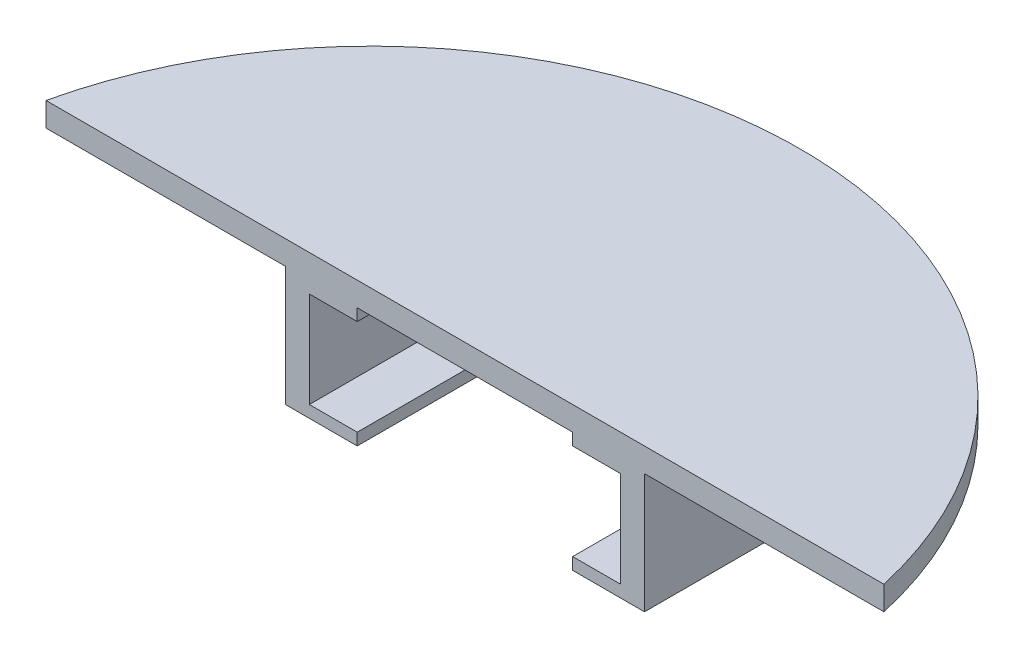
SolidWorks part; units mm, degrees
ref_plane "Front Plane" through (0, 0, 0) normal (0, 0, 1) x (1, 0, 0)
ref_plane "Top Plane" through (0, 0, 0) normal (0, 1, 0) x (1, 0, 0)
ref_plane "Right Plane" through (0, 0, 0) normal (1, 0, 0) x (0, 0, -1)
sketch "Sketch1" plane through (0, 0, 0) normal (0, 1, 0) x (1, 0, 0)
  line L0 (-13, 0) -> (-13, -13)
  line L1 (13, 0) -> (13, -13)
  line L2 (15, 0) -> (15, -13)
  line L3 (-15, 0) -> (-15, -13)
  line L4 (-35, -13) -> (35, -13)
  line L5 (-9, 0) -> (-9, -13)
  line L6 (9, 0) -> (9, -13)
  circle A0 centre (0, 0) radius 13 construction
  circle A2 centre (0, 0) radius 15 construction
  arc A3 (13, 0) -> (-13, 0) centre (0, 0) ccw
  arc A4 (15, 0) -> (-15, 0) centre (0, 0) ccw
  arc A5 (-35, -13) -> (35, -13) centre (0, -20.875) cw
  arc A6 (-32.9469, -13) -> (32.9469, -13) centre (0, -20.875) cw
  circle A7 centre (0, 0) radius 9
  dimension "D1" = 26
  dimension "D2" = 2
  dimension "D7" = 18
  dimension "D3" = 13
  dimension "D5" = 20
  dimension "D6" = 20
  dimension "D4" = 2
extrude "Boss-Extrude1" add sketch "Sketch1" along normal blind 2 contours A6 L4 L3 A4 | A6 A4 L2 L4 | L1 A3 L0 L4 A7 | A7 | A6 A3 L1 L4 L2 A4 | A6 A4 L3 L4 L0 A3 | A4 A6 | L4 A6 A4 A5 | A4 A6 L4 A5 | A5 L4 region at (-8.9324, 0, -8.9324) region at (-13.3002, 0, 6.5) region at (4.7242, 0, -12.3658) region at (0, 0, -13.5358) region at (-21.4914, 0, 3.7909) region at (-24.8424, 0, -2.8091) region at (21.4914, 0, 3.7909) region at (5.1556, 0, -14.5625) region at (0, 0, 0)
extrude "Boss-Extrude3" add sketch "Sketch1<5>" against normal blind 9 contours A6 A3 L1 L4 L2 A4 | A4 A6 | A6 A4 L3 L4 L0 A3 region at (-13.3002, 0, 6.5) region at (4.7242, 0, -12.3658) region at (0, 0, -13.5358)
sketch "Sketch1<5>" plane through (0, 0, 0) normal (0, 1, 0) x (1, 0, 0) same geometry as "Sketch1"
extrude "Boss-Extrude4" add sketch "Sketch1<6>" against normal blind 1 contours A7 L6 L4 L1 A3 L0 L5 region at (-8.9324, 0, -8.9324)
sketch "Sketch1<6>" plane through (0, 0, 0) normal (0, 1, 0) x (1, 0, 0) same geometry as "Sketch1"
extrude "Boss-Extrude5" add sketch "Sketch1<7>" against normal blind 1 from surface contours A6 A4 L3 L4 L0 A3 | A4 A6 | A6 A3 L1 L4 L2 A4 | A7 L6 L4 L1 A3 L0 L5 region at (-8.9324, 0, -8.9324) region at (-13.3002, 0, 6.5) region at (4.7242, 0, -12.3658) region at (0, 0, -13.5358) starting at face at (0, -9, 3)
sketch "Sketch1<7>" plane through (0, 0, 0) normal (0, 1, 0) x (1, 0, 0) same geometry as "Sketch1"
